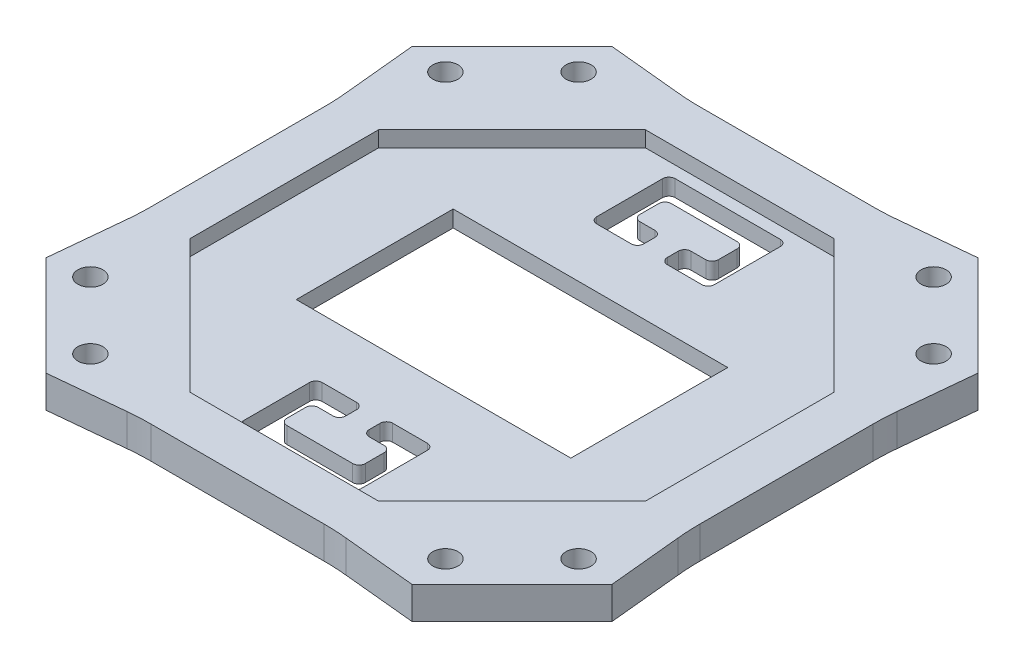
SolidWorks part; units mm, degrees
ref_plane "Front Plane" through (0, 0, 0) normal (0, 0, 1) x (1, 0, 0)
ref_plane "Top Plane" through (0, 0, 0) normal (0, 1, 0) x (1, 0, 0)
ref_plane "Right Plane" through (0, 0, 0) normal (1, 0, 0) x (0, 0, -1)
sketch "Sketch2" plane through (0, 0, 0) normal (0, 1, 0) x (1, 0, 0)
  line L0 (0, 0) -> (84.8528, 84.8528) construction
  line L1 (-35, -35) -> (35, -35) construction
  line L2 (-35, -35) -> (-35, 35) construction
  line L3 (-35, 35) -> (35, 35) construction
  line L4 (35, -35) -> (35, 35) construction
  line L5 (-35, -35) -> (35, 35) construction
  line L6 (-35, 35) -> (35, -35) construction
  line L7 (0, 35) -> (0, -35) construction
  line L8 (-12.5, 35) -> (12.5, 35)
  line L9 (35, 12.5) -> (35, -12.5)
  line L10 (12.5, -35) -> (-12.5, -35)
  line L11 (-35, -12.5) -> (-35, 12.5)
  line L12 (20.5061, 33.234) -> (33.234, 20.5061) construction
  line L13 (23.3345, 36.0624) -> (36.0624, 23.3345)
  line L14 (12.5, 35) -> (23.3345, 36.0624)
  line L15 (35, 12.5) -> (36.0624, 23.3345)
  line L16 (35, -12.5) -> (36.0624, -23.3345)
  line L17 (36.0624, -23.3345) -> (23.3345, -36.0624)
  line L18 (12.5, -35) -> (23.3345, -36.0624)
  line L19 (-12.5, -35) -> (-23.3345, -36.0624)
  line L20 (-23.3345, -36.0624) -> (-36.0624, -23.3345)
  line L21 (-35, -12.5) -> (-36.0624, -23.3345)
  line L22 (-35, 12.5) -> (-36.0624, 23.3345)
  line L23 (-36.0624, 23.3345) -> (-23.3345, 36.0624)
  line L24 (-12.5, 35) -> (-23.3345, 36.0624)
  circle A0 centre (22.6274, 31.1127) radius 1.6
  circle A1 centre (31.1127, 22.6274) radius 1.6
  circle A2 centre (22.6274, -31.1127) radius 1.6
  circle A3 centre (31.1127, -22.6274) radius 1.6
  circle A4 centre (-31.1127, -22.6274) radius 1.6
  circle A5 centre (-22.6274, -31.1127) radius 1.6
  circle A6 centre (-22.6274, 31.1127) radius 1.6
  circle A7 centre (-31.1127, 22.6274) radius 1.6
  point P0 (0, 0)
  point P13 (0, 35)
  point P22 (0, 0)
  point P23 (42.4264, 42.4264)
  point P25 (26.8701, 26.8701)
  point P27 (29.6985, 29.6985)
  point P58 (0, 0)
  dimension "D6" = 3.2
  dimension "D10" = 6
  dimension "D1" = 70
  dimension "D2" = 70
  dimension "D3" = 120
  dimension "D4" = 25
  dimension "D5" = 4
  dimension "D7" = 82
  dimension "D8" = 4
  dimension "D9" = 18
  dimension "D11" = 6
  dimension "D12" = 4
extrude "Boss-Extrude1" add sketch "Sketch2" along normal blind 4.1
sketch "Sketch4" plane through (0, 4.1, 0) normal (0, 1, 0) x (1, 0, 0)
  line L0 (12.5, 35) -> (-12.5, 35) construction
  line L1 (29, 12.0122) -> (12.0122, 29)
  line L2 (12.0122, 29) -> (-12.0122, 29)
  line L3 (-12.0122, 29) -> (-29, 12.0122)
  line L4 (-29, 12.0122) -> (-29, -12.0122)
  line L5 (-29, -12.0122) -> (-12.0122, -29)
  line L6 (-12.0122, -29) -> (12.0122, -29)
  line L7 (12.0122, -29) -> (29, -12.0122)
  line L8 (29, -12.0122) -> (29, 12.0122)
  line L9 (-35, 12.5) -> (-35, -12.5) construction
  line L11 (-36.0624, -23.3345) -> (-23.3345, -36.0624) construction
  circle A0 centre (0, 0) radius 29 construction
  dimension "D1" = 6
  dimension "D2" = 13
extrude "Cut-Extrude1" cut sketch "Sketch4" against normal blind 2
sketch "Sketch5" plane through (0, 2.1, 0) normal (0, 1, 0) x (1, 0, 0)
  line L0 (0, 29) -> (0, 0) construction
  line L1 (12.0122, 29) -> (-12.0122, 29) construction
  line L2 (0, 0) -> (-29, 0) construction
  line L3 (-29, 12.0122) -> (-29, -12.0122) construction
  line L4 (-24.8162, 10.2155) -> (-16.8162, 6.78)
  line L5 (-15, 4.0234) -> (-15, -4.0234)
  line L6 (-16.8162, -6.78) -> (-24.8162, -10.2155)
  line L7 (-29, -7.4589) -> (-29, 7.4589)
  line L8 (10.2155, 24.8162) -> (6.78, 16.8162)
  line L9 (-7.4589, 29) -> (7.4589, 29)
  line L10 (-6.78, 16.8162) -> (-10.2155, 24.8162)
  line L11 (4.0234, 15) -> (-4.0234, 15)
  line L12 (24.8162, -10.2155) -> (16.8162, -6.78)
  line L13 (29, 7.4589) -> (29, -7.4589)
  line L14 (16.8162, 6.78) -> (24.8162, 10.2155)
  line L15 (15, -4.0234) -> (15, 4.0234)
  line L16 (-10.2155, -24.8162) -> (-6.78, -16.8162)
  line L17 (7.4589, -29) -> (-7.4589, -29)
  line L18 (6.78, -16.8162) -> (10.2155, -24.8162)
  line L19 (-4.0234, -15) -> (4.0234, -15)
  arc A0 (-16.8162, 6.78) -> (-15, 4.0234) centre (-18, 4.0234) cw
  arc A1 (-15, -4.0234) -> (-16.8162, -6.78) centre (-18, -4.0234) cw
  arc A2 (-24.8162, -10.2155) -> (-29, -7.4589) centre (-26, -7.4589) cw
  arc A3 (-24.8162, 10.2155) -> (-29, 7.4589) centre (-26, 7.4589) ccw
  arc A4 (-10.2155, 24.8162) -> (-7.4589, 29) centre (-7.4589, 26) cw
  arc A5 (-4.0234, 15) -> (-6.78, 16.8162) centre (-4.0234, 18) cw
  arc A6 (6.78, 16.8162) -> (4.0234, 15) centre (4.0234, 18) cw
  arc A7 (10.2155, 24.8162) -> (7.4589, 29) centre (7.4589, 26) ccw
  arc A8 (24.8162, 10.2155) -> (29, 7.4589) centre (26, 7.4589) cw
  arc A9 (15, 4.0234) -> (16.8162, 6.78) centre (18, 4.0234) cw
  arc A10 (16.8162, -6.78) -> (15, -4.0234) centre (18, -4.0234) cw
  arc A11 (24.8162, -10.2155) -> (29, -7.4589) centre (26, -7.4589) ccw
  arc A12 (10.2155, -24.8162) -> (7.4589, -29) centre (7.4589, -26) cw
  arc A13 (4.0234, -15) -> (6.78, -16.8162) centre (4.0234, -18) cw
  arc A14 (-6.78, -16.8162) -> (-4.0234, -15) centre (-4.0234, -18) cw
  arc A15 (-10.2155, -24.8162) -> (-7.4589, -29) centre (-7.4589, -26) ccw
  point P17 (-15, 6)
  point P20 (-15, -6)
  point P23 (-29, -12.0122)
  point P26 (-29, 12.0122)
  point P65 (0, 0)
  dimension "D3" = 3
  dimension "D1" = 15
  dimension "D2" = 12
  dimension "D4" = 4
extrude "Cut-Extrude2" [suppressed] cut sketch "Sketch5" against normal blind 1.5
sketch "Sketch6" plane through (0, 2.1, 0) normal (0, 1, 0) x (1, 0, 0)
  line L1 (0, 0) -> (15.25, 0) construction
  line L2 (0, 0) -> (0, 15.25) construction
  line L3 (0, 15.25) -> (15.25, 15.25) construction
  line L4 (15.25, 0) -> (15.25, 15.25) construction
  circle A0 centre (15.25, 15.25) radius 1.5
  dimension "D2" = 3
  dimension "D1" = 15.25
extrude "Cut-Extrude3" [suppressed] cut sketch "Sketch6" against normal through all
sketch "Sketch7" [suppressed] plane through (0, 2, 0) normal (0, 1, 0) x (1, 0, 0)
  circle A0 centre (15.25, 15.25) radius 4
  circle A1 centre (15.25, 15.25) radius 1.5 construction
  circle A2 centre (15.25, 15.25) radius 1.5
  dimension "D1" = 8
extrude "Boss-Extrude4" [suppressed] add sketch "Sketch7" along normal blind 1.5
ref_axis "Axis1" [suppressed] through (0, 4.2, 0) along (0, -1, 0)
pattern_circular "CirPattern1" [suppressed] count 4 over 360 about axis through (0, 4.2, 0) along (0, -1, 0) of bodies 107
fillet "Fillet2" [suppressed] radius 2
fillet "Fillet4" radius 30 8 edges at (-35, 2.05, -12.5) (-35, 2.05, 12.5) (-12.5, 2.05, -35) (12.5, 2.05, -35) (35, 2.05, -12.5) (35, 2.05, 12.5) (12.5, 2.05, 35) (-12.5, 2.05, 35)
sketch "Sketch8" plane through (0, 2.1, 0) normal (0, 1, 0) x (1, 0, 0)
  line L0 (0, 26.4815) -> (0, 0) construction
  line L1 (0, 0) -> (-26.5298, 0) construction
  line L2 (-1.5, 19.7) -> (-1.5, 18.3)
  line L3 (-6.7, 17.5) -> (-2.3, 17.5)
  line L4 (-7.5, 18.3) -> (-7.5, 26.7)
  line L5 (-6.7, 27.5) -> (6.7, 27.5)
  line L6 (7.5, 18.3) -> (7.5, 26.7)
  line L7 (-7.5, 17.5) -> (7.5, 27.5) construction
  line L8 (-7.5, 27.5) -> (7.5, 17.5) construction
  line L9 (-4.2, 20.5) -> (-2.3, 20.5)
  line L10 (-5, 21.3) -> (-5, 23.7)
  line L11 (-4.2, 24.5) -> (4.2, 24.5)
  line L12 (5, 21.3) -> (5, 23.7)
  line L13 (-5, 20.5) -> (5, 24.5) construction
  line L14 (-5, 24.5) -> (5, 20.5) construction
  line L15 (1.5, 19.7) -> (1.5, 18.3)
  line L16 (2.3, 20.5) -> (4.2, 20.5)
  line L17 (2.3, 17.5) -> (6.7, 17.5)
  line L18 (-7.5, -18.3) -> (-7.5, -26.7)
  line L19 (-6.7, -27.5) -> (6.7, -27.5)
  line L20 (7.5, -18.3) -> (7.5, -26.7)
  line L21 (2.3, -17.5) -> (6.7, -17.5)
  line L22 (1.5, -19.7) -> (1.5, -18.3)
  line L23 (2.3, -20.5) -> (4.2, -20.5)
  line L24 (5, -21.3) -> (5, -23.7)
  line L25 (-4.2, -24.5) -> (4.2, -24.5)
  line L26 (-5, -21.3) -> (-5, -23.7)
  line L27 (-4.2, -20.5) -> (-2.3, -20.5)
  line L28 (-1.5, -19.7) -> (-1.5, -18.3)
  line L29 (-6.7, -17.5) -> (-2.3, -17.5)
  arc A0 (1.5, 18.3) -> (2.3, 17.5) centre (2.3, 18.3) ccw
  arc A1 (1.5, 19.7) -> (2.3, 20.5) centre (2.3, 19.7) cw
  arc A2 (-1.5, 18.3) -> (-2.3, 17.5) centre (-2.3, 18.3) cw
  arc A3 (-1.5, 19.7) -> (-2.3, 20.5) centre (-2.3, 19.7) ccw
  arc A4 (4.2, 20.5) -> (5, 21.3) centre (4.2, 21.3) ccw
  arc A5 (-5, 23.7) -> (-4.2, 24.5) centre (-4.2, 23.7) cw
  arc A6 (-4.2, 20.5) -> (-5, 21.3) centre (-4.2, 21.3) cw
  arc A7 (4.2, 24.5) -> (5, 23.7) centre (4.2, 23.7) cw
  arc A8 (6.7, 17.5) -> (7.5, 18.3) centre (6.7, 18.3) ccw
  arc A9 (-7.5, 26.7) -> (-6.7, 27.5) centre (-6.7, 26.7) cw
  arc A10 (-6.7, 17.5) -> (-7.5, 18.3) centre (-6.7, 18.3) cw
  arc A11 (6.7, 27.5) -> (7.5, 26.7) centre (6.7, 26.7) cw
  arc A12 (-7.5, -26.7) -> (-6.7, -27.5) centre (-6.7, -26.7) ccw
  arc A13 (6.7, -27.5) -> (7.5, -26.7) centre (6.7, -26.7) ccw
  arc A14 (6.7, -17.5) -> (7.5, -18.3) centre (6.7, -18.3) cw
  arc A15 (1.5, -18.3) -> (2.3, -17.5) centre (2.3, -18.3) cw
  arc A16 (1.5, -19.7) -> (2.3, -20.5) centre (2.3, -19.7) ccw
  arc A17 (4.2, -20.5) -> (5, -21.3) centre (4.2, -21.3) cw
  arc A18 (4.2, -24.5) -> (5, -23.7) centre (4.2, -23.7) ccw
  arc A19 (-5, -23.7) -> (-4.2, -24.5) centre (-4.2, -23.7) ccw
  arc A20 (-4.2, -20.5) -> (-5, -21.3) centre (-4.2, -21.3) ccw
  arc A21 (-1.5, -19.7) -> (-2.3, -20.5) centre (-2.3, -19.7) cw
  arc A22 (-1.5, -18.3) -> (-2.3, -17.5) centre (-2.3, -18.3) ccw
  arc A23 (-6.7, -17.5) -> (-7.5, -18.3) centre (-6.7, -18.3) ccw
  point P3 (0, 22.5)
  point P9 (0, 22.5)
  point P20 (1.5, 17.5)
  point P23 (1.5, 20.5)
  point P26 (-1.5, 17.5)
  point P29 (-1.5, 20.5)
  dimension "D7" = 0.8
  dimension "D1" = 17.5
  dimension "D2" = 15
  dimension "D3" = 10
  dimension "D4" = 2.5
  dimension "D5" = 3
  dimension "D6" = 6
extrude "Cut-Extrude4" cut sketch "Sketch8" against normal through all
sketch "Sketch9" plane through (0, 2.1, 0) normal (0, 1, 0) x (1, 0, 0)
  line L1 (-17.5, -10) -> (17.5, -10)
  line L2 (-17.5, -10) -> (-17.5, 10)
  line L3 (-17.5, 10) -> (17.5, 10)
  line L4 (17.5, -10) -> (17.5, 10)
  line L5 (-17.5, -10) -> (17.5, 10) construction
  line L6 (-17.5, 10) -> (17.5, -10) construction
  point P0 (0, 0)
  dimension "D1" = 35
  dimension "D2" = 20
extrude "Cut-Extrude5" cut sketch "Sketch9" against normal through all
